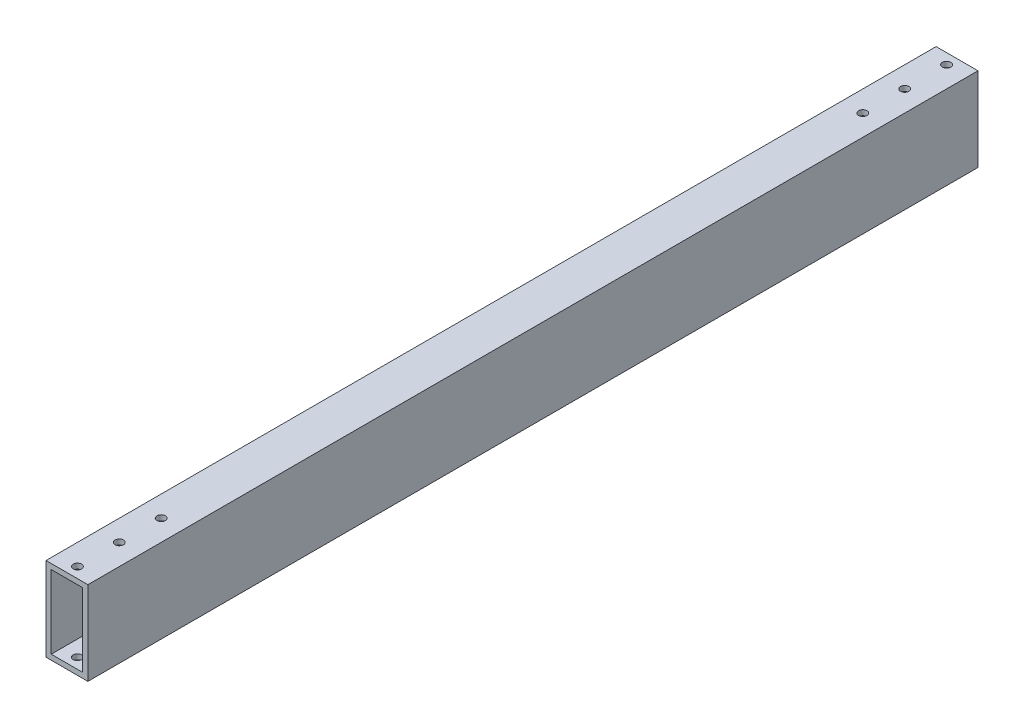
SolidWorks part; units mm, degrees
ref_plane "Front" through (0, 0, 0) normal (0, 0, 1) x (1, 0, 0)
ref_plane "Top" through (0, 0, 0) normal (0, 1, 0) x (1, 0, 0)
ref_plane "Right" through (0, 0, 0) normal (1, 0, 0) x (0, 0, -1)
sketch "Sketch1" plane through (0, 0, 0) normal (0, 0, 1) x (1, 0, 0)
  line L1 (-12.7, -25.4) -> (12.7, -25.4)
  line L2 (-12.7, -25.4) -> (-12.7, 25.4)
  line L3 (-12.7, 25.4) -> (12.7, 25.4)
  line L4 (12.7, -25.4) -> (12.7, 25.4)
  line L5 (-12.7, -25.4) -> (12.7, 25.4) construction
  line L6 (-12.7, 25.4) -> (12.7, -25.4) construction
  point P0 (0, 0)
  dimension "D1" = 25.4
  dimension "D2" = 50.8
extrude "Extrude-Thin1" add sketch "Sketch1" along normal blind 539.75 thin thin type one direction reverse wall 3.175
hole_wizard "#10 Clearance Hole2" positions "Sketch4" profile "Sketch5" hole size "#10" standard "ANSI Inch" end condition through all
sketch "Sketch4" plane through (0, 25.4, 0) normal (0, 1, 0) x (1, 0, 0)
  line L0 (12.7, -539.75) -> (-12.7, -539.75) construction
  line L1 (-12.7, -539.75) -> (-12.7, 0) construction
  line L2 (12.7, 0) -> (-12.7, 0) construction
  point P0 (0, -533.4)
  point P2 (0, -508)
  point P4 (0, -482.6)
  point P6 (0, -533.4)
  point P8 (0, -508)
  point P10 (0, -533.4)
  point P23 (0, -6.35)
  point P25 (0, -31.75)
  point P27 (0, -57.15)
  point P28 (0, 0)
  dimension "D1" = 6.35
  dimension "D2" = 25.4
  dimension "D3" = 25.4
  dimension "D4" = 12.7
  dimension "D5" = 6.35
  dimension "D6" = 25.4
  dimension "D7" = 25.4
sketch "Sketch5" plane through (0, 25.4, 533.4) normal (1, 0, 0) x (0, 0, 1)
  line L0 (0, 0) -> (0, 50.8)
  line L1 (0, 50.8) -> (2.5527, 50.8)
  line L2 (2.5527, 50.8) -> (2.5527, 0)
  line L5 (2.5527, 0) -> (0, 0)
  line L11 (0, -6.35) -> (0, 107.95) construction
  dimension "Thru Hole Dia." = 5.1054
  dimension "Thru Hole Depth" = 50.8
